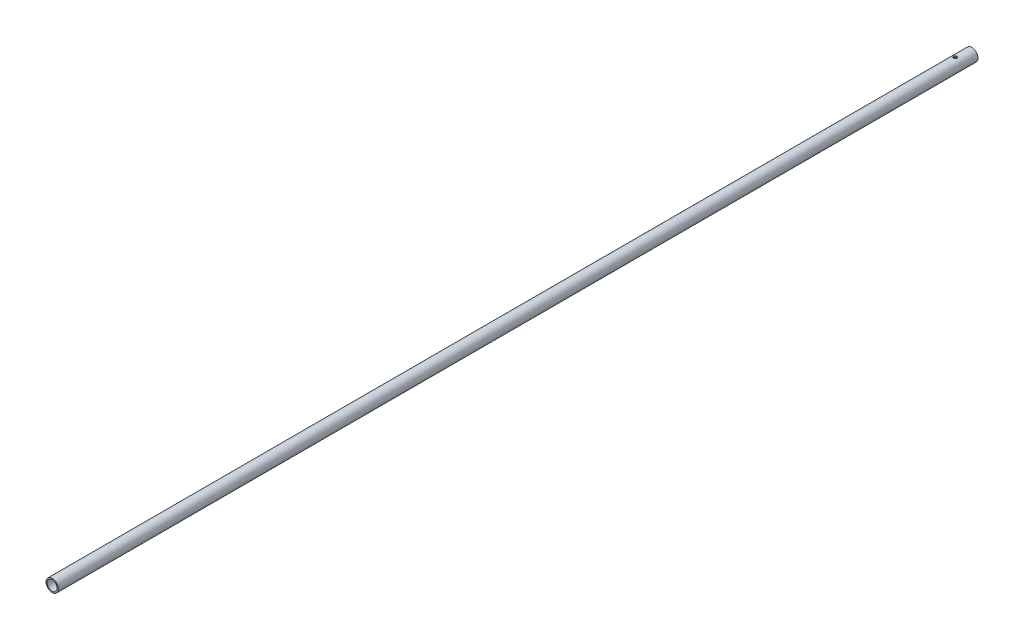
SolidWorks part; units mm, degrees
material "Hexcel AS4C (3000 Filaments)"
ref_plane "Front Plane" through (0, 0, 0) normal (0, 0, 1) x (1, 0, 0)
ref_plane "Top Plane" through (0, 0, 0) normal (0, 1, 0) x (1, 0, 0)
ref_plane "Right Plane" through (0, 0, 0) normal (1, 0, 0) x (0, 0, -1)
sketch "Sketch1" plane through (0, 0, 0) normal (0, 0, 1) x (1, 0, 0)
  circle A0 centre (0, 0) radius 3.048
  circle A1 centre (0, 0) radius 3.7592
  dimension "D1" = 6.096
  dimension "D2" = 0.7112
extrude "Boss-Extrude1" add sketch "Sketch1" along normal blind 558.8
sketch "Sketch2" plane through (0, 0, 0) normal (0, 1, 0) x (1, 0, 0)
  circle A0 centre (0, -10.16) radius 1.016
  dimension "D1" = 2.032
  dimension "D2" = 10.16
extrude "Cut-Extrude1" cut sketch "Sketch2" against normal up to surface and the other way up to surface up to face at (3.7592, 0, 558.8) other way up to face at (3.7592, 0, 558.8)
